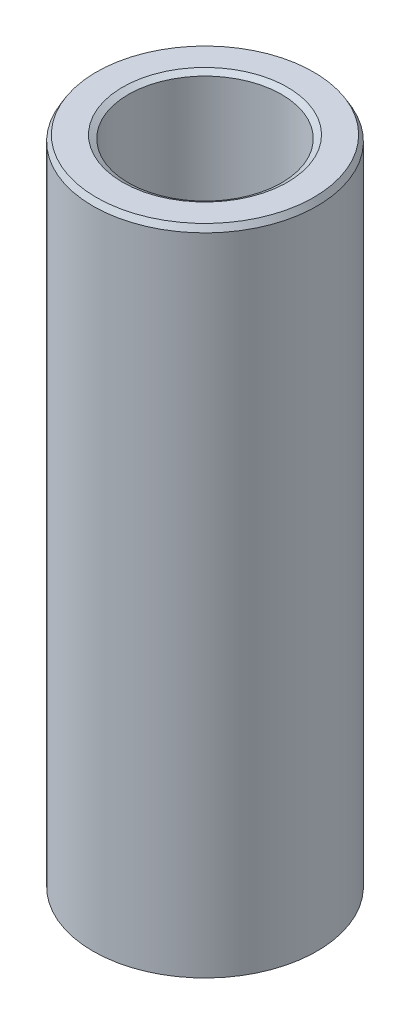
SolidWorks part; units mm, degrees
ref_plane "Front Plane" through (0, 0, 0) normal (0, 0, 1) x (1, 0, 0)
ref_plane "Top Plane" through (0, 0, 0) normal (0, 1, 0) x (1, 0, 0)
ref_plane "Right Plane" through (0, 0, 0) normal (1, 0, 0) x (0, 0, -1)
sketch "Sketch1" plane through (0, 0, 0) normal (0, 1, 0) x (1, 0, 0)
  circle A0 centre (0, 0) radius 27.5
  dimension "SLEEVE_OD" = 55
extrude "Boss-Extrude1" add sketch "Sketch1" along normal blind 160.6557
sketch "Sketch2" plane through (0, 0, 0) normal (0, 1, 0) x (1, 0, 0)
  circle A0 centre (0, 0) radius 18.8032
  dimension "BORE_D" = 37.6064
extrude "Cut-Extrude1" cut sketch "Sketch2" along normal through all
chamfer "Chamfer1" distance 1.4306 angle 30 4 edges at (0, 160.6557, 18.8032) (0, 0, 18.8032) (0, 0, 27.5) (0, 160.6557, 27.5) first distance on face at (0, 160.6557, 18.8032) first distance on face at (0, 0, 18.8032) first distance on face at (0, 160.6557, 27.5)
